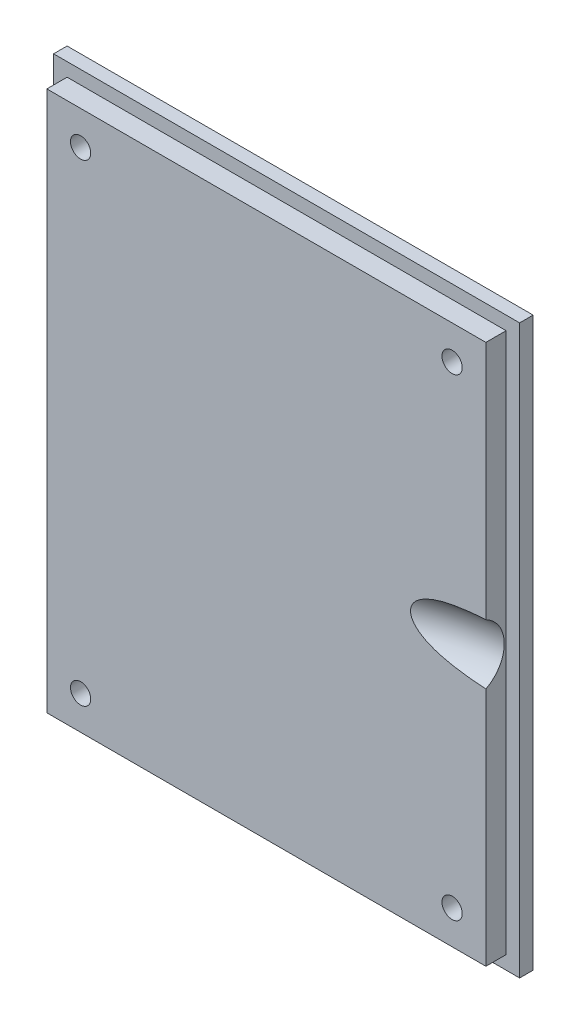
SolidWorks part; units mm, degrees
material "ABS"
ref_plane "前视基准面" through (0, 0, 0) normal (0, 0, 1) x (1, 0, 0)
ref_plane "上视基准面" through (0, 0, 0) normal (0, 1, 0) x (1, 0, 0)
ref_plane "右视基准面" through (0, 0, 0) normal (1, 0, 0) x (0, 0, -1)
sketch "草图1" plane through (0, 0, 0) normal (0, 0, 1) x (1, 0, 0)
  line L0 (-32.5, -40) -> (-32.5, 40)
  line L1 (-37.5, -45) -> (37.5, -45)
  line L2 (-37.5, -45) -> (-37.5, 45)
  line L3 (-37.5, 45) -> (37.5, 45)
  line L4 (37.5, -45) -> (37.5, 45)
  line L5 (-37.5, -45) -> (37.5, 45) construction
  line L6 (-37.5, 45) -> (37.5, -45) construction
  line L7 (-32.5, 40) -> (32.5, 40)
  line L8 (32.5, -40) -> (32.5, 40)
  line L9 (-32.5, -40) -> (32.5, -40)
  line L10 (-34.5, -42) -> (-34.5, 42)
  line L11 (-34.5, 42) -> (34.5, 42)
  line L12 (34.5, -42) -> (34.5, 42)
  line L13 (-34.5, -42) -> (34.5, -42)
  point P0 (0, 0)
  dimension "D1" = 75
  dimension "D2" = 90
  dimension "D3" = 5
  dimension "D4" = 2
extrude "凸台-拉伸1" add sketch "草图1" along normal blind 5 contours L0 L7 L8 L9
extrude "凸台-拉伸2" add sketch "草图1<3>" along normal blind 2 contours L10 L13 L12 L11 L9 L0 L7 L8 region at (-33.4129, 0, 0)
sketch "草图1<3>" plane through (0, 0, 0) normal (0, 0, 1) x (1, 0, 0) same geometry as "草图1"
sketch "草图3" plane through (0, 0, 0) normal (0, 1, 0) x (1, 0, 0)
  line L1 (37.5, 0) -> (37.5, -4.1568) construction
  line L4 (-37.5, 0) -> (37.5, 0) construction
  arc A0 (37.5, -7) -> (17.5, -12.359) centre (37.5, -47) ccw
  dimension "D1" = 40
  dimension "D2" = 7
  dimension "D3" = 30
sweep "切除-扫描1" cut path "草图3" circular profile diameter 10 parameters "D3"=10
sketch "草图8" plane through (0, 0, 0) normal (0, 0, -1) x (-1, 0, 0)
  line L0 (0, 0) -> (0, 18.9134) construction
  line L1 (-66.3937, 0) -> (-56.848, 0) construction
  line L2 (37.5, 45) -> (-37.5, 45) construction
  line L3 (-37.5, -45) -> (-37.5, 45) construction
  circle A0 centre (-27.5, 35) radius 1.5
  circle A1 centre (27.5, 35) radius 1.5
  circle A2 centre (27.5, -35) radius 1.5
  circle A3 centre (-27.5, -35) radius 1.5
  dimension "D1" = 3
  dimension "D2" = 10
  dimension "D3" = 10
extrude "切除-拉伸1" cut sketch "草图8" against normal through all
